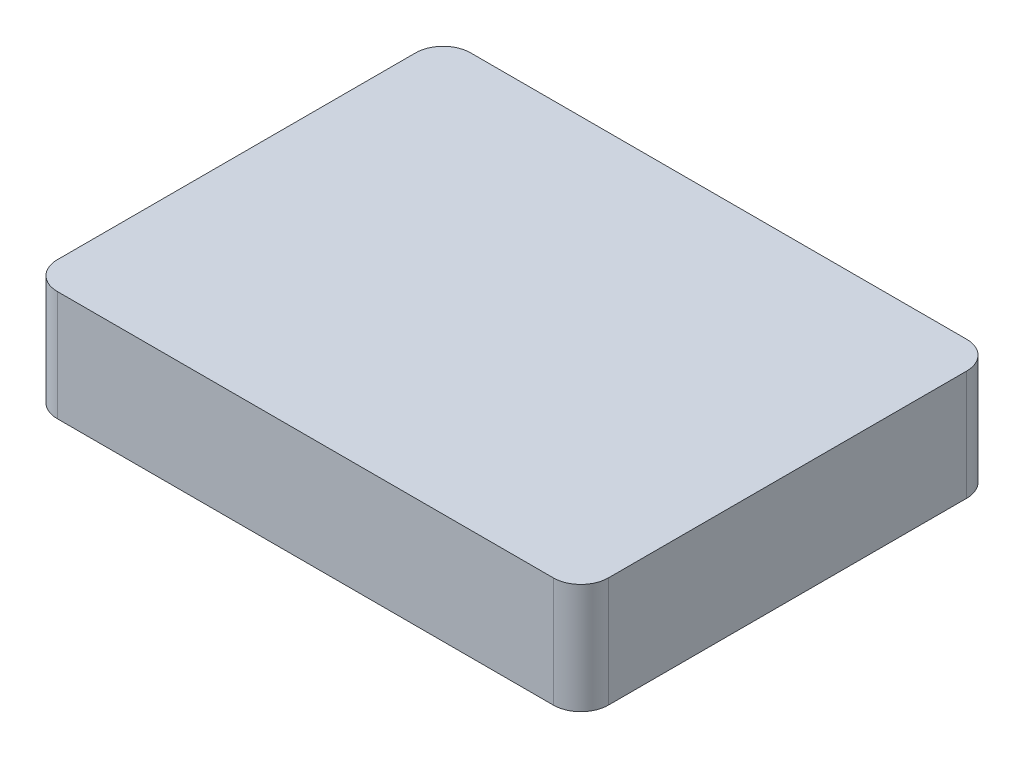
SolidWorks part; units mm, degrees
ref_plane "Front Plane" through (0, 0, 0) normal (0, 0, 1) x (1, 0, 0)
ref_plane "Top Plane" through (0, 0, 0) normal (0, 1, 0) x (1, 0, 0)
ref_plane "Right Plane" through (0, 0, 0) normal (1, 0, 0) x (0, 0, -1)
sketch "Sketch1" plane through (0, 0, 0) normal (0, 1, 0) x (1, 0, 0)
  line L0 (0, 0) -> (12.7, 0)
  line L1 (12.7, 0) -> (12.7, 9.525)
  line L2 (12.7, 9.525) -> (0, 9.525)
  line L3 (0, 9.525) -> (0, 0)
  dimension "D1" = 12.7
  dimension "D2" = 9.525
extrude "Boss-Extrude1" add sketch "Sketch1" along normal blind 2.54
fillet "Fillet1" radius 0.635 4 edges at (0, 1.27, -9.525) (12.7, 1.27, -9.525) (12.7, 1.27, 0) (0, 1.27, 0)
shell "Shell1" thickness 0.635 removed face at (6.35, 0, -4.7625)
sketch "Sketch2" plane through (0, 1.905, 0) normal (0, -1, 0) x (-1, 0, 0)
  line L0 (-0.635, 4.7625) -> (-12.065, 4.7625) construction
  line L1 (-0.635, 8.89) -> (-0.635, 0.635) construction
  line L2 (-12.065, 0.635) -> (-12.065, 8.89) construction
  line L3 (-6.35, 0.635) -> (-6.35, 8.89) construction
  line L4 (-0.635, 0.635) -> (-12.065, 0.635) construction
  line L5 (-12.065, 8.89) -> (-0.635, 8.89) construction
  circle A0 centre (-6.35, 4.7625) radius 2.54
  dimension "D1" = 5.08
extrude "Boss-Extrude2" add sketch "Sketch2" along normal up to surface (1.905 mm away) up to face at (6.35, 0, -4.7625)
